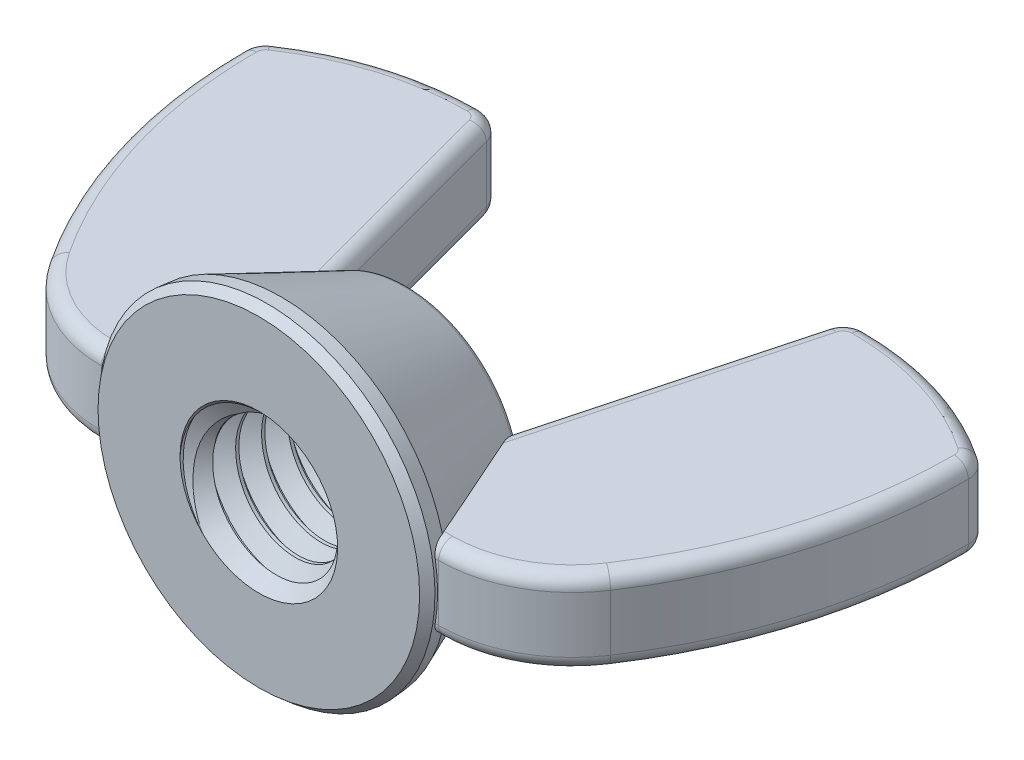
SolidWorks part; units mm, degrees
ref_plane "Front Plane" through (0, 0, 0) normal (0, 0, 1) x (1, 0, 0)
ref_plane "Top Plane" through (0, 0, 0) normal (0, 1, 0) x (1, 0, 0)
ref_plane "Right Plane" through (0, 0, 0) normal (1, 0, 0) x (0, 0, -1)
sketch "Sketch1" plane through (0, 0, 0) normal (0, 0, 1) x (1, 0, 0)
  circle A0 centre (0, 0) radius 2.413
  circle A1 centre (0, 0) radius 5.1594
  dimension "D1" = 10.3187
sketch "Sketch2" plane through (0, 0, 0) normal (0, 1, 0) x (1, 0, 0)
  line L0 (0, 0) -> (0, 12.7) construction
  line L1 (-2.413, 0) -> (2.413, 0) construction
  line L2 (-11.1125, 12.7) -> (11.1125, 12.7) construction
  line L3 (11.1125, 12.7) -> (11.1125, 0) construction
  line L4 (-11.1125, 12.7) -> (-11.1125, 0) construction
  line L5 (-11.1125, 0) -> (11.1125, 0) construction
  line L6 (-3.5186, 4.572) -> (3.5186, 4.572) construction
  line L7 (0, 0) -> (0, 4.572) construction
  line L8 (-4.3144, 0.6858) -> (5.1594, 0.6858) construction
  line L9 (5.1594, 0) -> (5.1594, 4.572) construction
  line L10 (3.1667, 4.572) -> (5.3943, 12.8856)
  line L12 (3.5186, 4.572) -> (3.5186, 0.3429) construction
  line L13 (-5.1594, 0) -> (5.1594, 0) construction
  line L14 (5.1594, 0.6858) -> (3.5186, 4.572) construction
  line L15 (5.3943, 12.8856) -> (11.3449, 11.0664)
  line L16 (11.3449, 11.0664) -> (7.152, 0.3429)
  line L17 (5.1594, 0.3429) -> (7.152, 0.3429)
  line L19 (3.1667, 0.3429) -> (5.1594, 0.3429)
  line L20 (-3.1667, 4.572) -> (3.1667, 4.572) construction
  line L21 (3.1667, 4.572) -> (3.1667, 0.3429)
  circle A3 centre (10.3959, 10.6072) radius 0.7166 construction
  circle A4 centre (5.8945, 11.9834) radius 0.7166 construction
  dimension "D6" = 1.4332
  dimension "D2" = 4.572
  dimension "D4" = 7.0371
  dimension "D1" = 0.6858
  dimension "D3" = 22.89
  dimension "D5" = 0.3429
  dimension "D8" = 17
  dimension "D9" = 6.3334
  dimension "D7" = 15
sketch "Sketch13" plane through (0, 0, 0) normal (0, 1, 0) x (1, 0, 0)
  line L1 (3.1667, 4.572) -> (3.1667, 0.3429) construction
  line L2 (3.1667, 4.572) -> (5.3943, 12.8856) construction
  line L3 (-11.1125, 12.7) -> (11.1125, 12.7) construction
  line L4 (11.1125, 12.7) -> (11.1125, 0) construction
  line L5 (5.1594, 0.3429) -> (7.152, 0.3429) construction
  line L6 (3.1667, 0.3429) -> (5.1594, 0.3429) construction
  line L7 (0, 0) -> (0, 4.572) construction
  line L8 (-2.413, 0) -> (2.413, 0) construction
  line L9 (0, 0) -> (0, 12.7) construction
  line L10 (-3.5186, 4.572) -> (3.5186, 4.572) construction
  line L11 (3.1667, 0.3429) -> (5.1594, 0.3429)
  line L12 (3.1667, 4.572) -> (3.1667, 0.3429)
  line L13 (3.1667, 4.572) -> (5.2023, 12.1689)
  circle A0 centre (10.3959, 10.6072) radius 0.7166 construction
  circle A1 centre (5.8945, 11.9834) radius 0.7166 construction
  arc A5 (11.1125, 10.6072) -> (10.7966, 11.2013) centre (10.3959, 10.6072) ccw
  arc A6 (5.8945, 12.7) -> (5.2023, 12.1689) centre (5.8945, 11.9834) ccw
  arc A7 (8.5807, 2.183) -> (11.1125, 10.6072) centre (-4.1686, 10.6072) ccw
  arc A8 (10.7966, 11.2013) -> (5.8945, 12.7) centre (5.8945, 3.9335) ccw
  arc A10 (5.1594, 0.3429) -> (8.5807, 2.183) centre (5.1594, 4.4437) ccw
extrude "Extrude2" add sketch "Sketch13" along normal mid plane 2.5797
sketch "Sketch3" plane through (0, 0, 0) normal (0, 0, 1) x (1, 0, 0)
  circle A0 centre (0, 0) radius 5.1594 construction
  circle A1 centre (0, 0) radius 5.1594
extrude "Extrude1" add sketch "Sketch3" against normal up to vertex (0.6858 mm away) draft 5 separate body up to point (5.1594, 0, -0.6858)
sketch "Sketch15" plane through (0, 0, -0.6858) normal (0, 0, -1) x (-1, 0, 0)
  circle A1 centre (0, 0) radius 5.0994
  circle A2 centre (0, 0) radius 5.0994
  dimension "D1" = 0
extrude "Extrude3" add sketch "Sketch15" along normal up to vertex (3.8862 mm away) draft 22.89 up to point (0, 0, -4.572)
fillet "Fillet3" radius 0.254 1 edges at (-3.4586, 0, -4.572)
sketch "Sketch12" plane through (0, 0, -4.572) normal (0, 0, -1) x (-1, 0, 0)
  circle A1 centre (0, 0) radius 5.0994
  circle A2 centre (0, 0) radius 5.0994 construction
  dimension "D1" = 10.1988
sketch "Sketch4" plane through (0, 0, 0) normal (0, 0, 1) x (1, 0, 0)
  circle A0 centre (0, 0) radius 2.413 construction
  circle A1 centre (0, 0) radius 2.413
extrude "Cut-Extrude1" cut sketch "Sketch4" against normal through all
sketch "Sketch5" plane through (0, 0, 0) normal (0, 0, 1) x (1, 0, 0)
  circle A0 centre (0, 0) radius 2.413 construction
  circle A1 centre (0, 0) radius 2.413
curve "Helix/Spiral1" pitch 0.7937 height 7.747 turns 9.76 parameters "pitch"=0.7937
sketch "Sketch6" plane through (0, 0, 0) normal (0, 1, 0) x (1, 0, 0)
  line L0 (-2.413, -0.6945) -> (-1.8974, -0.3969)
  line L1 (-1.8974, -0.3969) -> (-1.8974, -0.2977)
  line L2 (-1.8974, -0.2977) -> (-2.413, 0)
  line L3 (-2.413, -0.6945) -> (-2.413, 0)
  line L4 (-2.413, -0.3473) -> (-1.8974, -0.3473) construction
  line L5 (-2.1552, -0.5457) -> (-2.1552, -0.1488) construction
  line L6 (-2.413, 0) -> (2.413, 0) construction
  dimension "D1" = 60
  dimension "D2" = 0.0992
  dimension "D3" = 0.3969
sweep "Sweep1" add profiles "Sketch6" path "Helix/Spiral1"
sketch "Sketch7" plane through (0, 0, 0) normal (0, 0, 1) x (1, 0, 0)
  circle A1 centre (0, 0) radius 5.1594
  circle A2 centre (0, 0) radius 5.1594
  dimension "D1" = 0
extrude "Cut-Extrude2" cut sketch "Sketch7" along normal through all
ref_plane "Plane1" through (0, 0, -4.572) normal (0, 0, 1) x (1, 0, 0)
sketch "Sketch8" plane through (0, 0, -4.572) normal (0, 0, 1) x (1, 0, 0)
  circle A0 centre (0, 0) radius 5.0994 construction
  circle A2 centre (0, 0) radius 5.0994
extrude "Cut-Extrude3" cut sketch "Sketch8" against normal through all
sketch "Sketch9" plane through (0, 0, 0) normal (0, 0, 1) x (1, 0, 0)
  circle A1 centre (0, 0) radius 2.413
  circle A2 centre (0, 0) radius 2.413
  dimension "D1" = 0
extrude "Cut-Extrude4" cut sketch "Sketch9" against normal through all draft 45
sketch "Sketch11" plane through (0, 0, -4.572) normal (0, 0, 1) x (1, 0, 0)
  circle A0 centre (0, 0) radius 2.413 construction
  circle A1 centre (0, 0) radius 2.3622
  circle A2 centre (0, 0) radius 2.413 construction
  dimension "D1" = 0.0508
extrude "Cut-Extrude5" cut sketch "Sketch11" along normal through all draft 45
chamfer "Chamfer1" distance 0.2572 angle 45 1 edges at (5.1594, 0, 0)
fillet "Fillet4" radius 0.4299 14 edges at (4.163, 1.2898, -0.3429) (7.1018, 1.2898, -0.8321) (5.4582, 1.2898, -12.5519) (8.4575, 1.2898, -12.3169) (11.0286, 1.2898, -10.9436) (4.163, -1.2898, -0.3429) (7.1018, -1.2898, -0.8321) (5.4582, -1.2898, -12.5519) (8.4575, -1.2898, -12.3169) (11.0286, -1.2898, -10.9436) (10.4659, 1.2898, -6.209) (10.4659, -1.2898, -6.209) (4.1845, 1.2898, -8.3704) (4.1845, -1.2898, -8.3704)
mirror "Mirror6" about plane through (0, 0, 0) normal (1, 0, 0) of bodies 108 113
combine bodies "Combine2" operation type add bodies to combine 116 108 107
equation "\"D1@Sketch1\" = \"thread dia@Sketch1\"*1.725"
equation "\"D2@Sketch2\" = \"B@Sketch2\"*.36"
equation "\"D3@Helix/Spiral1\" = \"D2@Sketch2\"+.125"
equation "\"D2@Sketch6\" = \"pitch@Helix/Spiral1\"*.125"
equation "\"D3@Sketch6\" = \"pitch@Helix/Spiral1\"*.5"
equation "\"D4@Sketch2\" = \"D1@Sketch12\"*.69"
equation "\"D1@Extrude2\" = \"D1@Sketch1\"*.25"
equation "\"D1@Sketch2\" = \"D2@Sketch2\"*.150"
equation "\"D5@Sketch2\" = \"D1@Sketch2\"/2"
equation "\"D3@Extrude3\" = \"D3@Sketch2\""
equation "\"D1@Chamfer1\" = \"D5@Sketch2\"*.75"
equation "\"D9@Sketch2\" = \"D4@Sketch2\"*.9"
equation "\"D6@Sketch2\" = \"D1@Extrude2\"/1.8"
equation "\"D1@Fillet4\" = \"D1@Extrude2\"/6"
